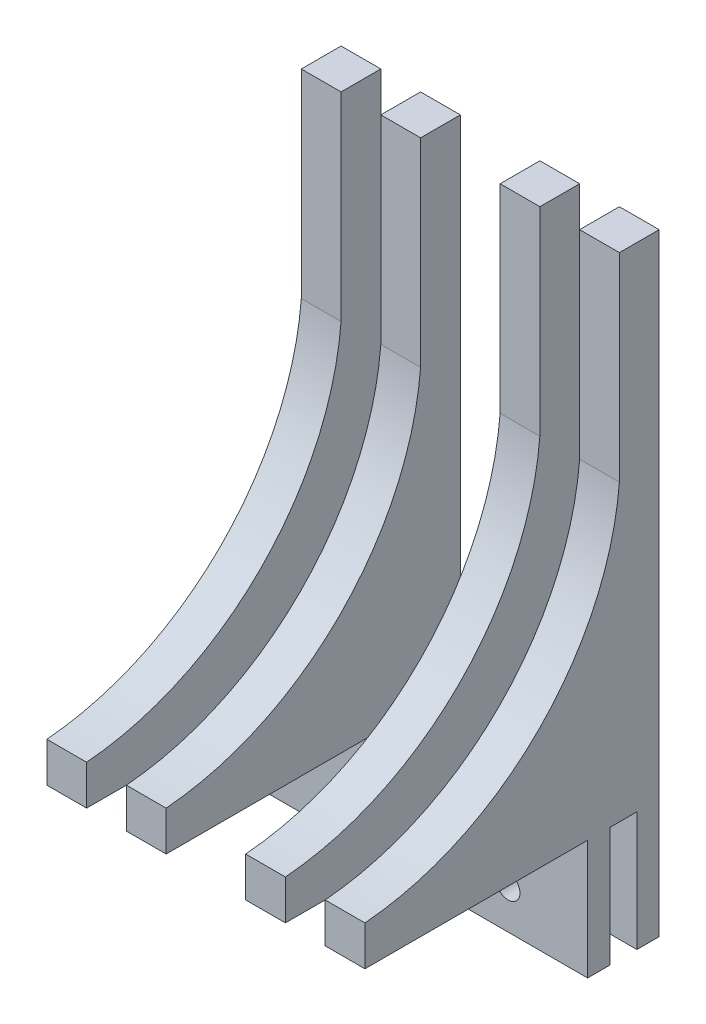
SolidWorks part; units mm, degrees
ref_plane "Front Plane" through (0, 0, 0) normal (0, 0, 1) x (1, 0, 0)
ref_plane "Top Plane" through (0, 0, 0) normal (0, 1, 0) x (1, 0, 0)
ref_plane "Right Plane" through (0, 0, 0) normal (1, 0, 0) x (0, 0, -1)
sketch "Sketch1" plane through (0, 0, 0) normal (1, 0, 0) x (0, 0, -1)
  line L0 (0, 0) -> (0, 23)
  line L1 (0, 23) -> (9, 23)
  line L2 (9, 23) -> (9, 0)
  line L8 (0, 0) -> (9, 0)
  dimension "D2" = 9
  dimension "D4" = 23
extrude "Boss-Extrude1" add sketch "Sketch1" along normal blind 40
ref_plane "Plane1" through (20, 0, 0) normal (-1, 0, 0) x (0, 0, 1)
sketch "Sketch3" plane through (0, 0, 0) normal (-1, 0, 0) x (0, 0, 1)
  line L0 (0, 0) -> (28, 0)
  line L1 (-9, 23) -> (-9, 37)
  line L3 (28, 0) -> (28, 5)
  line L5 (-9, 23) -> (0, 23)
  line L6 (-9, 37) -> (-9, 62)
  line L7 (0, 0) -> (0, 23)
  line L8 (-9, 62) -> (-4, 62)
  line L9 (-4, 62) -> (-4, 37)
  arc A0 (-4, 37) -> (28, 5) centre (30.8812, 39.8812) ccw
  dimension "D1" = 35
  dimension "D2" = 37
  dimension "D3" = 37
  dimension "D4" = 5
  dimension "D5" = 5
  dimension "D6" = 25
  dimension "D7" = 5
extrude "Boss-Extrude2" add sketch "Sketch3" against normal blind 5
pattern_linear "LPattern1" count 2 spacing 10 along (1, 0, 0) of "Boss-Extrude2"
sketch "Sketch6" plane through (0, 0, 0) normal (0, -1, 0) x (1, 0, 0)
  line L0 (40, 0) -> (40, -9) construction
  line L1 (0, -9) -> (40, -9)
  line L2 (0, -9) -> (0, -6.2)
  line L3 (0, -6.2) -> (40, -6.2)
  line L4 (40, -9) -> (40, -6.2)
  line L5 (0, 28) -> (0, -9) construction
  line L6 (40, 0) -> (0, 0)
  line L7 (40, 0) -> (40, -2.8)
  line L8 (40, -2.8) -> (0, -2.8)
  line L9 (0, 0) -> (0, -2.8)
  dimension "D1" = 3.4
extrude "Boss-Extrude4" add sketch "Sketch6" along normal blind 15
sketch "Sketch7" plane through (0, 0, 28) normal (0, 0, 1) x (1, 0, 0)
  line L0 (10, 37) -> (10, 5) construction
  line L1 (5, 0) -> (10, 0)
  line L2 (5, 0) -> (5, 23)
  line L3 (5, 23) -> (10, 23)
  line L4 (10, 0) -> (10, 23)
  line L5 (10, 23) -> (10, 0) construction
  line L6 (20, 4.95) -> (20, -4.95) construction
  line L7 (20, 23) -> (15, 23)
  line L8 (20, 23) -> (20, 0)
  line L9 (20, 0) -> (15, 0)
  line L10 (15, 23) -> (15, 0)
  line L11 (40, 23) -> (15, 23) construction
  line L12 (15, 23) -> (15, 0) construction
extrude "Cut-Extrude1" cut sketch "Sketch7" against normal through all
sketch "Sketch8" plane through (0, 0, 0) normal (0, 0, 1) x (1, 0, 0)
  line L2 (0, -15) -> (0, 0) construction
  line L3 (10, 0) -> (5, 0) construction
  circle A0 centre (10, -10) radius 1.5
  circle A3 centre (20, -10) radius 1.5
  circle A4 centre (30, -10) radius 1.5
  dimension "D1" = 3
  dimension "D2" = 10
  dimension "D3" = 10
  dimension "D4" = 3
  dimension "D5" = 10
extrude "Cut-Extrude2" cut sketch "Sketch8" against normal through all
mirror "Mirror1" about plane through (20, 0, 0) normal (-1, 0, 0) of "LPattern1", "Cut-Extrude1", "Boss-Extrude2"
